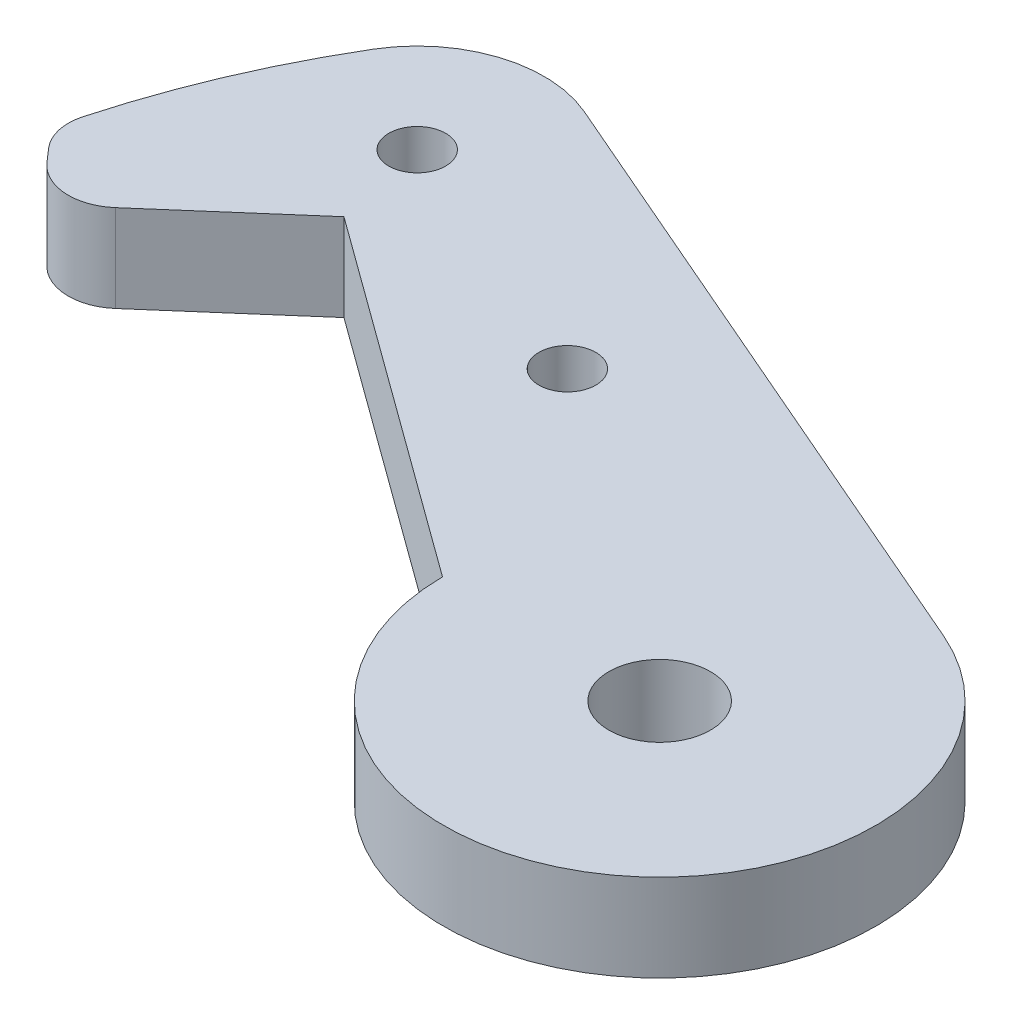
SolidWorks part; units mm, degrees
ref_plane "Front" through (0, 0, 0) normal (0, 0, 1) x (1, 0, 0)
ref_plane "Top" through (0, 0, 0) normal (0, 1, 0) x (1, 0, 0)
ref_plane "Right" through (0, 0, 0) normal (1, 0, 0) x (0, 0, -1)
ref_axis "side-side" through (80.9, 0, 0) along (-1, 0, 0)
ref_axis "up-down" through (0, 50, 0) along (0, -1, 0)
ref_axis "front-back" through (0, 0, -80.9) along (0, 0, 1)
sketch "Sketch2" plane through (0, 0, 0) normal (0, 1, 0) x (1, 0, 0)
  line L1 (-36.3831, 16.847) -> (-151.2834, -83.2712)
  point P2 (0, 0)
  point P3 (0, 0)
  point P4 (0, 0)
sketch "Sketch1" plane through (0, 0, 0) normal (0, 1, 0) x (1, 0, 0)
  line L0 (-36.3831, 16.847) -> (-28.1218, 7.366) construction
  line L2 (-36.0756, 16.3422) -> (-13.4998, -0.0747)
  line L3 (-48.2987, 10.0023) -> (-49.0144, 10.8238)
  line L4 (-42.3473, 13.9694) -> (-41.1986, 12.6511) construction
  line L5 (-34.2596, 29.5434) -> (5.3636, 12.3888)
  line L7 (-36.3831, 16.847) -> (-151.2834, -83.2712) construction
  line L8 (-43.7133, 9.6871) -> (-36.0756, 16.3422)
  arc A0 (-43.7133, 9.6871) -> (-48.2987, 10.0023) centre (-45.8484, 12.1374) cw
  arc A1 (-49.6462, 13.5865) -> (-44.2347, 26.3178) centre (0, 0) cw
  arc A2 (-49.6462, 13.5865) -> (-49.0144, 10.8238) centre (-46.7526, 12.7946) ccw
  arc A3 (-34.2596, 29.5434) -> (-44.2347, 26.3178) centre (-37.4133, 22.2593) ccw
  arc A5 (-13.4998, -0.0747) -> (5.3636, 12.3888) centre (0, 0) ccw
  arc A7 (-44.8796, 24.9532) -> (-31.4102, 17.0663) centre (-37.4133, 22.2593) ccw construction
  circle A10 centre (8, 0) radius 1.75 construction
  circle A11 centre (0, -8) radius 1.75 construction
  circle A12 centre (-8, 0) radius 1.75 construction
  circle A13 centre (0, 8) radius 1.75 construction
  circle A14 centre (-20.8625, 15.0937) radius 1.778
  circle A15 centre (0, 0) radius 3.175
  circle A16 centre (-20.8625, 15.0937) radius 7.9375 construction
  circle A18 centre (-37.4133, 22.2593) radius 1.778
  point P0 (-37.4529, 17.3438)
  point P2 (-48.6478, 7.2575)
  point P11 (-51.3007, 11.1854)
  point P21 (-36.0756, 16.3422)
  point P23 (-36.4799, 16.6363)
  dimension "D2" = 3
  dimension "D4" = 13.5
  dimension "D5" = 0.5
  dimension "D8" = 3.25
  dimension "D7" = 6.3871
  dimension "D11" = 15.875
  dimension "D13" = 6.35
  dimension "D14" = 3.556
  dimension "D1" = 13
  dimension "D3" = 8
  dimension "D12" = 25.75
extrude "Boss-Extrude1" add sketch "Sketch1" along normal blind 5.461
